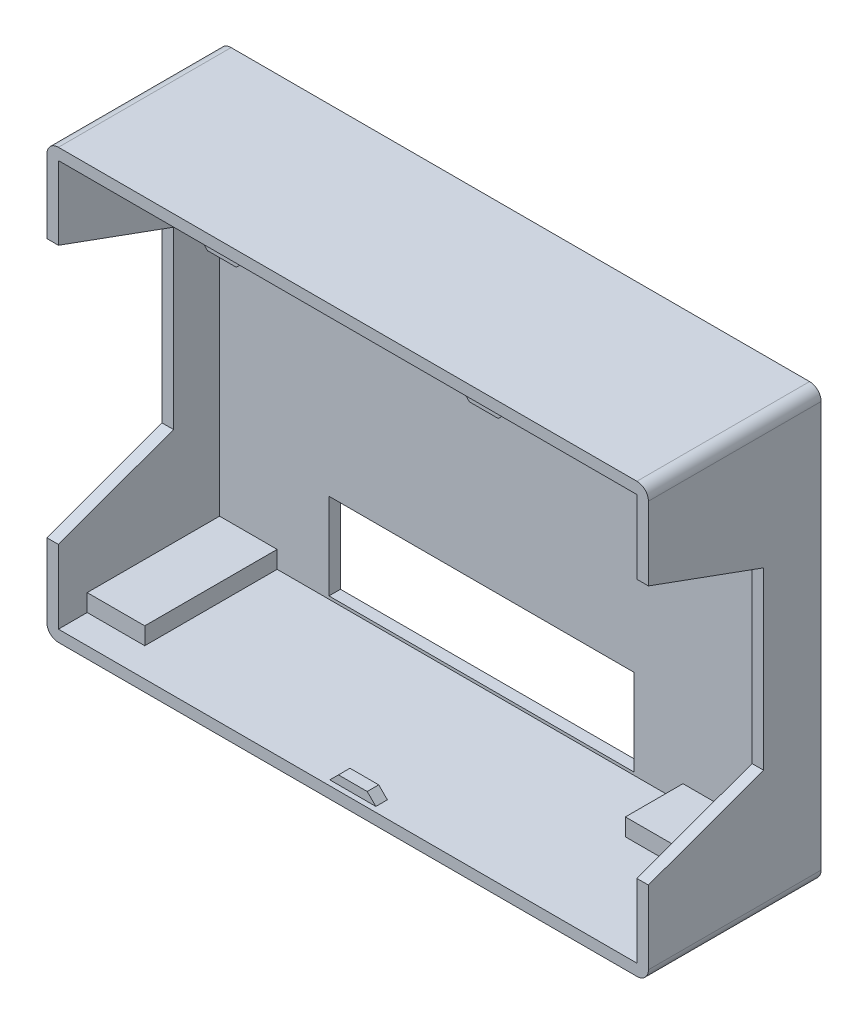
SolidWorks part; units mm, degrees
ref_plane "Front Plane" through (0, 0, 0) normal (1, 0, 0) x (0, 1, 0)
ref_plane "Top Plane" through (0, 0, 0) normal (0, 0, 1) x (0, 1, 0)
ref_plane "Right Plane" through (0, 0, 0) normal (0, 1, 0) x (-1, 0, 0)
sketch "Sketch1" plane through (0, 0, 0) normal (0, 0, 1) x (0, 1, 0)
  line L0 (-37.25, -52.25) -> (-37.25, 52.25)
  line L1 (-35.25, -50.25) -> (35.25, -50.25)
  line L2 (-35.25, -50.25) -> (-35.25, 50.25)
  line L3 (-35.25, 50.25) -> (35.25, 50.25)
  line L4 (35.25, -50.25) -> (35.25, 50.25)
  line L5 (-35.25, -50.25) -> (35.25, 50.25) construction
  line L6 (-35.25, 50.25) -> (35.25, -50.25) construction
  line L7 (-37.25, 52.25) -> (37.25, 52.25)
  line L8 (37.25, -52.25) -> (37.25, 52.25)
  line L9 (-37.25, -52.25) -> (37.25, -52.25)
  point P0 (0, 0)
  dimension "D1" = 70.5
  dimension "D2" = 100.5
  dimension "D3" = 2
extrude "Boss-Extrude1-above-board-surface" add sketch "Sketch1" along normal blind 5
sketch "Sketch2" plane through (0, 0, 0) normal (0, 0, -1) x (1, 0, 0)
  line L0 (50.25, -35.25) -> (-50.25, -35.25) construction
  line L1 (-50.25, 35.25) -> (50.25, 35.25) construction
  line L2 (50.25, -35.25) -> (-50.25, -35.25) construction
  line L3 (-50.25, 35.25) -> (50.25, 35.25) construction
  line L4 (52.25, -37.25) -> (52.25, 37.25)
  line L5 (52.25, 37.25) -> (-52.25, 37.25)
  line L6 (-52.25, 37.25) -> (-52.25, -37.25)
  line L7 (-52.25, -37.25) -> (52.25, -37.25)
  line L8 (52.25, -37.25) -> (52.25, 37.25)
  line L9 (52.25, 37.25) -> (-52.25, 37.25)
  line L10 (-52.25, 37.25) -> (-52.25, -37.25)
  line L11 (-52.25, -37.25) -> (52.25, -37.25)
  line L12 (-50.25, 32.25) -> (-40.25, 32.25)
  line L14 (-50.25, 32.25) -> (-50.25, -32.25)
  line L15 (50.25, 35.25) -> (50.25, -35.25)
  line L16 (-40.25, 32.25) -> (-40.25, 35.25)
  line L17 (-40.25, 35.25) -> (50.25, 35.25)
  line L19 (-70.7302, 0) -> (65.1142, 0) construction
  line L20 (-50.25, -35.25) -> (-50.25, 35.25) construction
  line L23 (-50.25, 32.25) -> (50.25, 32.25) construction
  line L25 (-40.25, -35.25) -> (50.25, -35.25)
  line L26 (-40.25, -32.25) -> (-40.25, -35.25)
  line L27 (-40.25, -32.25) -> (-50.25, -32.25)
  dimension "D4" = 10
  dimension "D1" = 0
  dimension "D2" = 3
extrude "Boss-Extrude2-under-23mm" add sketch "Sketch2" along normal blind 23
sketch "Sketch3" plane through (0, 0, -23) normal (0, 0, -1) x (1, 0, 0)
  line L1 (-52.25, 37.25) -> (52.25, 37.25)
  line L2 (-52.25, 37.25) -> (-52.25, -37.25)
  line L3 (-52.25, -37.25) -> (52.25, -37.25)
  line L4 (52.25, 37.25) -> (52.25, -37.25)
extrude "Boss-Extrude3-bottom-cover-2mm" add sketch "Sketch3" along normal blind 2
ref_plane "Plane1-pcb-up-surface-2.1mm" through (0, 0, 2.1) normal (0, 0, 1) x (1, 0, 0)
sketch "Sketch4" plane through (0, 0, 2.1) normal (0, 0, 1) x (1, 0, 0)
  line L0 (52.25, 37.25) -> (-52.25, 37.25) construction
  line L1 (-25.25, 37.25) -> (-20.25, 37.25)
  line L2 (-25.25, 37.25) -> (-25.25, 33.75)
  line L4 (-20.25, 37.25) -> (-20.25, 33.75)
  line L6 (0, 0) -> (0, 44.7823) construction
  line L7 (-25.25, 33.75) -> (-20.25, 33.75)
  line L9 (50.25, 35.25) -> (-50.25, 35.25) construction
  line L10 (-40.25, 32.25) -> (-40.25, 35.25) construction
  line L17 (25.25, 33.75) -> (20.25, 33.75)
  line L18 (20.25, 37.25) -> (20.25, 33.75)
  line L19 (25.25, 37.25) -> (25.25, 33.75)
  line L20 (25.25, 37.25) -> (20.25, 37.25)
  line L21 (0, 0) -> (0, -57.7369) construction
  line L22 (-52.25, -37.25) -> (52.25, -37.25) construction
  line L23 (-2.5, -33.75) -> (2.5, -33.75)
  line L24 (-2.5, -33.75) -> (-2.5, -37.25)
  line L25 (-2.5, -37.25) -> (2.5, -37.25)
  line L26 (2.5, -33.75) -> (2.5, -37.25)
  line L27 (-2.5, -33.75) -> (2.5, -37.25) construction
  line L28 (-2.5, -37.25) -> (2.5, -33.75) construction
  line L29 (-50.25, -35.25) -> (50.25, -35.25) construction
  point P1 (0, -35.5)
  dimension "D1" = 1.5
  dimension "D2" = 1.5
  dimension "D3" = 15
  dimension "D4" = 5
  dimension "D5" = 5
extrude "Boss-Extrude4-anchor-pins" add sketch "Sketch4" along normal blind 2
sketch "Sketch5" plane through (0, 0, 5) normal (0, 0, 1) x (1, 0, 0)
  line L1 (-75, -22.5) -> (75, -22.5)
  line L2 (-75, -22.5) -> (-75, 22.5)
  line L3 (-75, 22.5) -> (75, 22.5)
  line L4 (75, -22.5) -> (75, 22.5)
  line L5 (-75, -22.5) -> (75, 22.5) construction
  line L6 (-75, 22.5) -> (75, -22.5) construction
  point P0 (0, 0)
  dimension "D1" = 45
  dimension "D2" = 150
extrude "Cut-Extrude1-cut-usb" cut sketch "Sketch5" against normal offset from surface 15 draft 20 up to face at (-45.25, -33.75, 0)
fillet "Fillet1" radius 2 4 edges at (-52.25, -37.25, -10) (-52.25, 37.25, -10) (52.25, 37.25, -10) (52.25, -37.25, -10)
chamfer "Chamfer2" distance 1.5 angle 45 6 edges at (20.25, 35.25, 3.1) (25.25, 35.25, 3.1) (-25.25, 35.25, 3.1) (-20.25, 35.25, 3.1) (2.5, -35.25, 3.1) (-2.5, -35.25, 3.1)
ref_plane "Plane1-lower-board-bottom-surface" through (0, 0, -13) normal (0, 0, 1) x (1, 0, 0)
sketch "Sketch6" plane through (0, 0, -13) normal (0, 0, 1) x (1, 0, 0)
  line L0 (50.25, -35.25) -> (-40.25, -35.25) construction
  line L1 (40.25, -35.25) -> (30.25, -35.25)
  line L2 (40.25, -35.25) -> (40.25, -32.25)
  line L3 (40.25, -32.25) -> (30.25, -32.25)
  line L4 (30.25, -35.25) -> (30.25, -32.25)
  line L7 (50.25, -35.25) -> (50.25, -22.5) construction
  line L8 (0, 0) -> (95.2761, 0) construction
  line L9 (30.25, 35.25) -> (30.25, 32.25)
  line L10 (40.25, 32.25) -> (30.25, 32.25)
  line L11 (40.25, 35.25) -> (40.25, 32.25)
  line L12 (40.25, 35.25) -> (30.25, 35.25)
  dimension "D1" = 3
  dimension "D2" = 10
  dimension "D3" = 10
extrude "Boss-Extrude1" add sketch "Sketch6" against normal up to surface (10 mm away) up to face at (-20.125, 0, -23)
sketch "Sketch7" plane through (0, 0, -23) normal (0, 0, 1) x (1, 0, 0)
  line L0 (-50.25, -32.25) -> (-50.25, 32.25) construction
  line L1 (-31.25, 34.75) -> (21.75, 34.75)
  line L2 (-31.25, 34.75) -> (-31.25, 19.75)
  line L3 (-31.25, 19.75) -> (21.75, 19.75)
  line L4 (21.75, 34.75) -> (21.75, 19.75)
  line L5 (50.25, 35.25) -> (-50.25, 35.25) construction
  line L6 (0, 0) -> (81.7021, 0) construction
  line L7 (21.75, -34.75) -> (21.75, -19.75)
  line L8 (-31.25, -19.75) -> (21.75, -19.75)
  line L9 (-31.25, -34.75) -> (-31.25, -19.75)
  line L10 (-31.25, -34.75) -> (21.75, -34.75)
  dimension "D1" = 19
  dimension "D2" = 0.5
  dimension "D3" = 15
  dimension "D4" = 53
extrude "Cut-Extrude1" cut sketch "Sketch7" against normal blind 10
